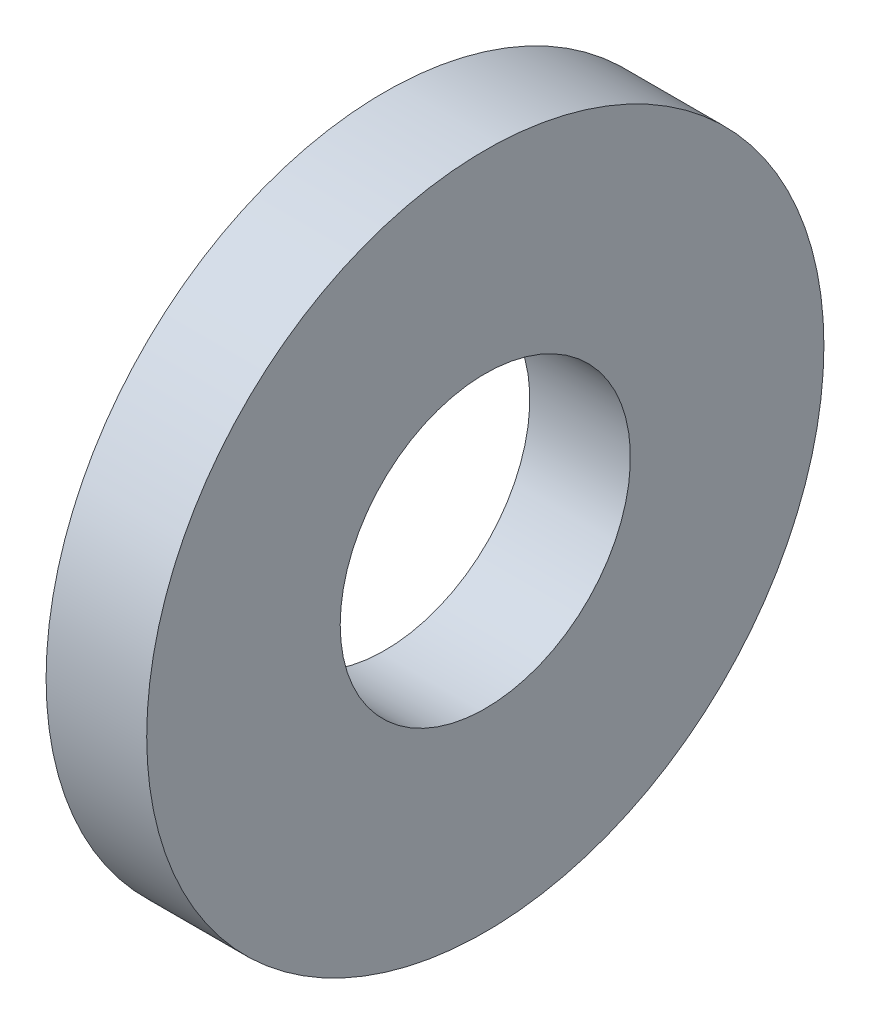
SolidWorks part; units mm, degrees
material "Plain Carbon Steel"
ref_plane "Front Plane" through (0, 0, 0) normal (0, 0, 1) x (1, 0, 0)
ref_plane "Top Plane" through (0, 0, 0) normal (0, 1, 0) x (1, 0, 0)
ref_plane "Right Plane" through (0, 0, 0) normal (1, 0, 0) x (0, 0, -1)
sketch "Sketch1" plane through (0, 0, 0) normal (1, 0, 0) x (0, 0, -1)
  circle A0 centre (0, 0) radius 5.5562
  circle A1 centre (0, 0) radius 2.3813
  dimension "OD" = 11.1125
  dimension "ID" = 4.7625
extrude "Boss-Extrude1" add sketch "Sketch1" along normal blind 1.651
